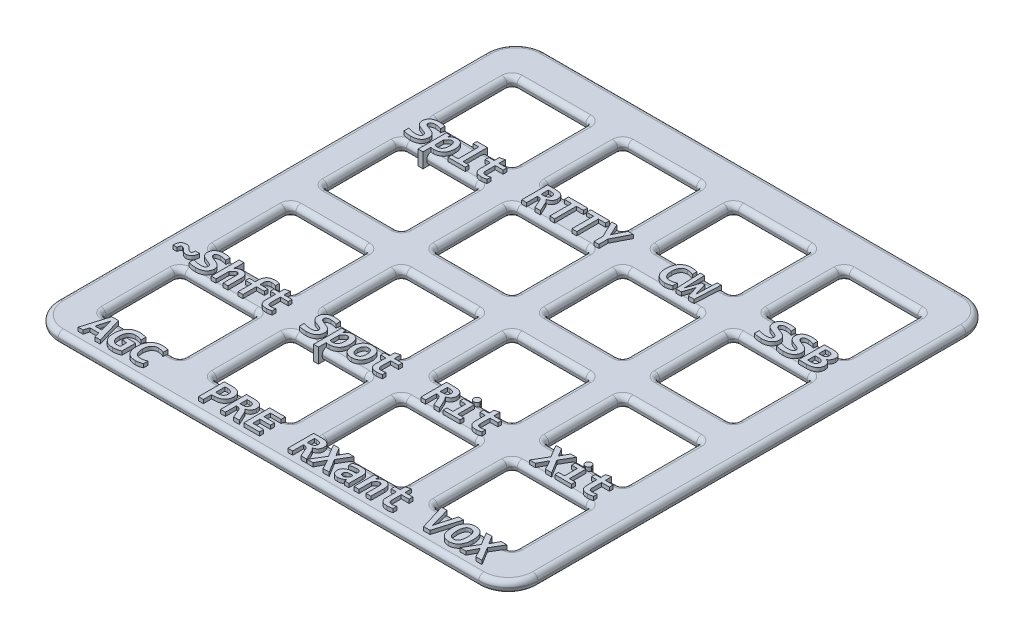
SolidWorks part; units mm, degrees
ref_plane "Front" through (0, 0, 0) normal (0, 0, 1) x (1, 0, 0)
ref_plane "Top" through (0, 0, 0) normal (0, 1, 0) x (1, 0, 0)
ref_plane "Right" through (0, 0, 0) normal (1, 0, 0) x (0, 0, -1)
sketch "Sketch1" plane through (0, 0, 0) normal (0, 1, 0) x (1, 0, 0)
  line L1 (-14.8807, -14.5355) -> (42.1193, -14.5355)
  line L2 (-18.8807, -18.5355) -> (-18.8807, -76.5355)
  line L3 (-14.8807, -80.5355) -> (42.1193, -80.5355)
  line L4 (46.1193, -18.5355) -> (46.1193, -76.5355)
  arc A0 (-14.8807, -14.5355) -> (-18.8807, -18.5355) centre (-14.8807, -18.5355) ccw
  arc A1 (46.1193, -18.5355) -> (42.1193, -14.5355) centre (42.1193, -18.5355) ccw
  arc A2 (42.1193, -80.5355) -> (46.1193, -76.5355) centre (42.1193, -76.5355) ccw
  arc A3 (-18.8807, -76.5355) -> (-14.8807, -80.5355) centre (-14.8807, -76.5355) ccw
  dimension "D1" = 65
  dimension "D2" = 66
extrude "main" add sketch "Sketch1" along normal blind 1.5
sketch "Sketch2" plane through (0, 1.5, 0) normal (0, 1, 0) x (1, 0, 0)
  line L0 (42.1193, -14.5355) -> (-14.8807, -14.5355) construction
  line L1 (-14.2307, -19.6855) -> (-3.5307, -19.6855)
  line L2 (-14.2307, -19.6855) -> (-14.2307, -30.3855)
  line L3 (-14.2307, -30.3855) -> (-3.5307, -30.3855)
  line L4 (-3.5307, -19.6855) -> (-3.5307, -30.3855)
  line L5 (-18.8807, -18.5355) -> (-18.8807, -76.5355) construction
  point P4 (-8.8807, -19.6855)
  dimension "D1" = 5.15
  dimension "D2" = 4.65
  dimension "D3" = 10.7
  dimension "D4" = 10.7
extrude "button hole 1" cut sketch "Sketch2" against normal through all
fillet "button fillet" radius 0.7 12 edges at (-8.8807, 0, 30.3855) (-8.8807, 1.5, 30.3855) (-8.8807, 0, 19.6855) (-8.8807, 1.5, 19.6855) (-3.5307, 0.75, 30.3855) (-3.5307, 0, 25.0355) (-3.5307, 0.75, 19.6855) (-3.5307, 1.5, 25.0355) (-14.2307, 0.75, 19.6855) (-14.2307, 0, 25.0355) (-14.2307, 0.75, 30.3855) (-14.2307, 1.5, 25.0355)
pattern_linear "buttons by 16" count 4 spacing 15 along (1, 0, 0) count 4 spacing 15 along (0, 0, 1) of "button fillet", "button hole 1"
fillet "outer edge fillet" radius 0.7 16 edges at (13.6193, 1.5, 14.5355) (13.6193, 0, 14.5355) (46.1193, 1.5, 47.5355) (46.1193, 0, 47.5355) (13.6193, 1.5, 80.5355) (13.6193, 0, 80.5355) (-18.8807, 1.5, 47.5355) (-18.8807, 0, 47.5355) (44.9477, 1.5, 15.7071) (44.9477, 1.5, 79.364) (-17.7092, 1.5, 79.364) (-17.7092, 1.5, 15.7071) (44.9477, 0, 15.7071) (44.9477, 0, 79.364) (-17.7092, 0, 79.364) (-17.7092, 0, 15.7071)
sketch "Lettering" plane through (0, 0, 0) normal (0, 1, 0) x (1, 0, 0)
  line L0 (45.4193, -49.1355) -> (-18.1807, -49.1355) construction
  line L1 (45.4783, -79.1355) -> (-16.5217, -79.1355) construction
  line L2 (45.4193, -76.5355) -> (45.4193, -18.5355) construction
  line L3 (-18.1807, -18.5355) -> (-18.1807, -76.5355) construction
  line L5 (45.4193, -64.1355) -> (-18.1807, -64.1355) construction
  line L6 (45.4193, -76.5355) -> (45.4193, -18.5355) construction
  line L7 (-18.1807, -18.5355) -> (-18.1807, -76.5355) construction
  line L8 (45.4193, -34.1355) -> (-18.1807, -34.1355) construction
  line L11 (-14.8807, -80.5355) -> (42.1193, -80.5355) construction
  text T0 "SSB" font "Consolas" height 3.5
  text T1 "CW" font "Consolas" height 3.5
  text T2 "RTTY" font "Consolas" height 3.5
  text T3 "Splt" font "Consolas" height 3.5
  text T4 "Xit" font "Consolas" height 3.5
  text T5 "Rit" font "Consolas" height 3.5
  text T6 "~Shft" font "Consolas" height 3.5
  text T7 "Spot" font "Consolas" height 3.5
  text T8 "VOX" font "Consolas" height 3.5
  text T9 "RXant" font "Consolas" height 3.5
  text T10 "PRE" font "Consolas" height 3.5
  text T11 "AGC" font "Consolas" height 3.5
  dimension "D1" = 46.4
  dimension "D2" = 16.4
  dimension "D3" = 1.4
  dimension "D4" = 31.4
extrude "lettering boss" add sketch "Lettering" along normal offset from surface (2 mm away) 0.5 up to face at (13.6193, 1.5, 47.5355) offset beyond the face yes
